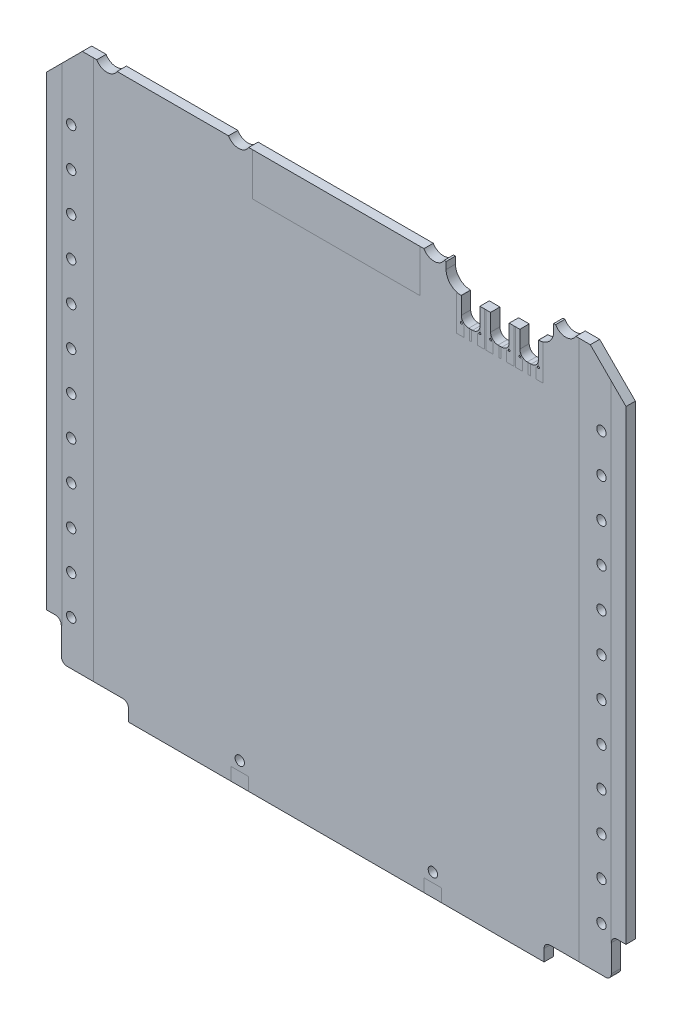
SolidWorks part; units mm, degrees
material "FR4_stuffedProtoboard"
ref_plane "Front Plane" through (0, 0, 0) normal (0, 0, 1) x (1, 0, 0)
ref_plane "Top Plane" through (0, 0, 0) normal (0, 1, 0) x (1, 0, 0)
ref_plane "Right Plane" through (0, 0, 0) normal (1, 0, 0) x (0, 0, -1)
ref_plane "Plane4" through (0, 0, -0.0125) normal (0, 0, -1) x (-1, 0, 0)
sketch "Sketch1" plane through (0, 0, -0.0125) normal (0, 0, -1) x (-1, 0, 0)
  line L4 (49.5, -50) -> (49.5, 45.3)
  line L6 (49.5, 45.3) -> (-49.5, 45.3)
  line L12 (-49.5, 45.3) -> (-49.5, -50)
  line L17 (-49.5, -50) -> (49.5, -50)
  line L18 (0, -50) -> (0, 45.3) construction
  dimension "D7" = 95.3
  dimension "D1" = 99
  dimension "D34" = 50
extrude "basicSize" add sketch "Sketch1" against normal blind 1.6
chamfer "Chamfer1" distance 6.1 angle 45 2 edges at (49.5, 45.3, 0.7875) (-49.5, 45.3, 0.7875)
sketch "Sketch4" plane through (0, 0, 1.5875) normal (0, 0, 1) x (1, 0, 0)
  line L1 (37.4679, 45.3) -> (40.9321, 45.3)
  line L7 (-43.4, 45.3) -> (43.4, 45.3) construction
  line L8 (49.5, 39.2) -> (49.5, -50) construction
  arc A0 (40.9321, 45.3) -> (37.4679, 45.3) centre (39.2, 46.3) cw
  point P5 (39.2, 44.3)
  dimension "D1" = 2
  dimension "D3" = 10.3
  dimension "D2" = 1
extrude "backplaneSideScrewCutout" cut sketch "Sketch4" against normal through all both and the other way through all
pattern_linear "LPattern3" count 2 spacing 22.5 along (-1, 0, 0) of "backplaneSideScrewCutout"
mirror "Mirror3" about plane through (0, 0, 0) normal (1, 0, 0) of "LPattern3"
sketch "Sketch6" plane through (0, 0, 1.5875) normal (0, 0, 1) x (1, 0, 0)
  line L0 (-49.5, -50) -> (-49.5, 39.2) construction
  line L1 (-49.5, -40.4) -> (-47, -40.4)
  line L2 (-49.5, -40.4) -> (-49.5, -50)
  line L4 (-47, -40.4) -> (-47, -47)
  line L5 (49.5, -50) -> (-49.5, -50) construction
  line L6 (-35.5, -50) -> (-49.5, -50)
  line L7 (-35.5, -50) -> (-35.5, -47)
  line L8 (-35.5, -47) -> (-47, -47)
  dimension "D1" = 2.5
  dimension "D2" = 3
  dimension "D3" = 9.6
  dimension "D4" = 14
extrude "Cut-Extrude4" cut sketch "Sketch6" against normal through all
fillet "Fillet1" radius 1 3 edges at (-35.5, -47, 0.7875) (-47, -47, 0.7875) (-47, -40.4, 0.7875)
mirror "Mirror1" about plane through (0, 0, 0) normal (1, 0, 0) of "Cut-Extrude4", "Fillet1"
sketch "Sketch7" plane through (0, 0, 1.5875) normal (0, 0, 1) x (1, 0, 0)
  line L0 (-14.2875, 45.5) -> (-14.2875, 39.912) construction
  line L1 (-14.2875, 45.3) -> (-14.2875, 38.007)
  line L2 (-12.2428, 38.007) -> (-11.8872, 38.007) construction
  line L3 (-14.2875, 38.007) -> (14.2875, 38.007)
  line L4 (14.2875, 45.5) -> (14.2875, 39.912) construction
  line L5 (14.2875, 45.3) -> (14.2875, 38.007)
  line L7 (-14.9679, 45.3) -> (14.9679, 45.3) construction
  line L8 (-14.2875, 45.3) -> (14.2875, 45.3)
extrude "TigerEyeFootprint" cut sketch "Sketch7" against normal blind 0.0001
sketch "thermalContacts_upper" plane through (0, 0, 1.5875) normal (0, 0, 1) x (1, 0, 0)
  line L0 (-49.5, -40.4) -> (-49.5, 39.2) construction
  line L1 (35.5, -50) -> (-35.5, -50) construction
  line L3 (-46.9, 45.3) -> (-46.9, -41.5)
  line L4 (-37.4679, 45.3) -> (-18.4321, 45.3) construction
  line L23 (-46.9, 45.3) -> (-56.3922, 45.3)
  line L24 (-56.3922, 45.3) -> (-56.3922, -41.5)
  line L25 (-56.3922, -41.5) -> (-46.9, -41.5)
  dimension "D1" = 2.6
  dimension "D2" = 8.5
extrude "keepOut_bottom" cut sketch "thermalContacts_upper" against normal blind 0.0001
sketch "Sketch3" plane through (0, 0, 1.5875) normal (0, 0, 1) x (1, 0, 0)
  line L1 (-47, -46) -> (-47, -41.5) construction
  line L2 (-36.5, -47) -> (-46, -47) construction
  line L3 (-14.9679, 45.3) -> (14.9679, 45.3) construction
  line L5 (-49.5, -40.4) -> (-49.5, 39.2) construction
  line L6 (-46.9, -41.5) -> (-46.9, 41.8) construction
  line L7 (-46.9, -41.5) -> (-47, -41.5)
  line L8 (-47, -46) -> (-47, -41.5) construction
  line L9 (-47, -41.5) -> (-46.9, -41.5) construction
  line L10 (0, -50) -> (0, 45.3) construction
  line L11 (35.5, -50) -> (-35.5, -50) construction
  line L12 (-43.4, 45.3) -> (-40.9321, 45.3) construction
  line L13 (-41.5, 45.3) -> (-46.9, 45.3)
  line L14 (-46, -47) -> (-41.5, -47)
  line L15 (-47, -41.5) -> (-47, -46)
  line L16 (-46.9, 45.3) -> (-46.9, -41.5)
  line L17 (-41.5, -47) -> (-41.5, 45.3)
  arc A3 (-47, -46) -> (-46, -47) centre (-46, -46) ccw construction
  arc A4 (-46, -47) -> (-47, -46) centre (-46, -46) cw
  dimension "D1" = 8
extrude "caution_top" cut sketch "Sketch3" against normal blind 0.0001
sketch "hold-downLocations" plane through (0, 0, 1.5875) normal (0, 0, 1) x (1, 0, 0)
  line L1 (-18, -47.8) -> (-15, -47.8) construction
  line L3 (15, -47.8) -> (18, -47.8)
  line L4 (18, -47.8) -> (18, -50)
  line L5 (35.5, -50) -> (-35.5, -50) construction
  line L6 (18, -50) -> (15, -50)
  line L7 (15, -50) -> (15, -47.8)
  line L8 (-15, -47.8) -> (-15, -50) construction
  line L9 (-15, -50) -> (-18, -50) construction
  line L10 (-18, -50) -> (-18, -47.8) construction
  line L11 (0, -50) -> (0, -47.8) construction
  line L12 (-15, -47.8) -> (15, -47.8) construction
  dimension "D1" = 3
  dimension "D2" = 2.2
  dimension "D3" = 3
  dimension "D5" = 30
extrude "hold-downFootprints" cut sketch "hold-downLocations" against normal blind 0.0001
ref_plane "midplane_Z" through (0, 0, 0.7875) normal (0, 0, 1) x (1, 0, 0)
mirror "clearances_top-bottom" about plane through (0, 0, 0.7875) normal (0, 0, 1) of "hold-downFootprints", "caution_top", "keepOut_bottom"
mirror "clearances_side-side" about plane through (0, 0, 0) normal (1, 0, 0) of "clearances_top-bottom"
sketch "Sketch10" plane through (0, 0, -0.0125) normal (0, 0, -1) x (-1, 0, 0)
  line L0 (-15, -47.8) -> (-15, -50) construction
  line L1 (-18, -47.8) -> (-15, -47.8)
  line L2 (-18, -47.8) -> (-18, -44.5)
  line L3 (-18, -44.5) -> (-15, -44.5)
  line L4 (-15, -47.8) -> (-15, -44.5)
  line L5 (-15, -50) -> (15, -50) construction
  line L6 (0, -50) -> (0, -41.5199) construction
  line L7 (15, -47.8) -> (15, -44.5)
  line L8 (18, -44.5) -> (15, -44.5)
  line L9 (18, -47.8) -> (18, -44.5)
  line L10 (18, -47.8) -> (15, -47.8)
  dimension "D1" = 5.5
extrude "bottomsideShelfKeepouts" cut sketch "Sketch10" against normal up to surface (0.0001 mm away) up to face at (16.5, -48.9, -0.0124)
sketch "recommendedBuildArea" [suppressed] plane through (0, 0, 1.5875) normal (0, 0, 1) x (1, 0, 0)
  line L0 (51.1146, 38.007) -> (51.1146, 56.8216) construction
  line L1 (-35.5, -45.5) -> (-46.8, -45.5) construction
  line L2 (-35.5, -47) -> (-35.5, -45.5) construction
  line L3 (35.5, -47) -> (35.5, -45.5) construction
  line L4 (14.2875, 45.3) -> (-14.2875, 45.3)
  line L5 (-14.2875, 45.3) -> (-14.2875, 38.007)
  line L6 (-14.2875, 38.007) -> (14.2875, 38.007)
  line L7 (-46.8, 41.9) -> (-49.5, 39.2)
  line L8 (-49.5, 39.2) -> (-49.5, -40.4)
  line L9 (-49.5, -40.4) -> (-48, -40.4)
  line L10 (-46.8, -41.5) -> (-46.8, 41.9)
  line L11 (-47, -41.4) -> (-47, -41.5)
  line L12 (-47, -41.4) -> (-47, -41.5)
  line L13 (-47, -41.5) -> (-46.8, -41.5)
  line L14 (35.5, -45.5) -> (46.8, -45.5) construction
  line L15 (54.1146, 35.007) -> (54.1146, 77.997)
  line L16 (54.1146, 77.997) -> (43.8, 42.325)
  line L17 (-46.8, -45.5) -> (-46.8, 41.9) construction
  line L20 (43.8, 42.325) -> (43.8, -42.5)
  line L21 (14.2875, 38.007) -> (14.2875, 45.3)
  line L22 (32.5, -42.5) -> (43.8, -42.5)
  line L23 (-14.2875, 45.3) -> (-14.2875, 38.007)
  line L24 (-14.2875, 38.007) -> (51.1146, 38.007)
  line L25 (32.5, -47) -> (32.5, -42.5)
  line L26 (32.5, -47) -> (32.5, -47)
  line L27 (21, -47) -> (32.5, -47)
  line L28 (21, -45) -> (21, -47)
  line L29 (46.8, -41.5) -> (47, -41.5)
  line L30 (46.8, -41.5) -> (47, -41.5)
  line L31 (46.8, 41.9) -> (46.8, -41.5)
  line L32 (48, -40.4) -> (49.5, -40.4)
  line L33 (49.5, -40.4) -> (49.5, 39.2)
  line L34 (49.5, 39.2) -> (46.8, 41.9)
  line L35 (47, -41.5) -> (47, -41.4)
  line L36 (12, -45) -> (21, -45)
  line L37 (47, -41.5) -> (47, -41.4)
  line L38 (46.8, 41.9) -> (46.8, -45.5) construction
  line L39 (12, -47) -> (12, -45)
  line L40 (-12, -47) -> (12, -47)
  line L41 (-12, -45) -> (-12, -47)
  line L42 (-21, -45) -> (-12, -45)
  line L43 (-21, -47) -> (-21, -45)
  line L44 (-32.5, -47) -> (-21, -47)
  line L45 (-32.5, -47) -> (-32.5, -47)
  line L46 (-32.5, -47) -> (-32.5, -42.5)
  line L47 (-32.5, -42.5) -> (-43.8, -42.5)
  line L48 (-43.8, -42.5) -> (-43.8, 34.7661)
  line L49 (-43.8, 34.7661) -> (-43.8, 34.7661)
  line L50 (-43.8, 34.7661) -> (-39.8793, 42.3)
  line L51 (-17.2875, 42.3) -> (-39.8793, 42.3)
  line L52 (-17.2875, 42.3) -> (-17.2875, 35.007)
  line L53 (-17.2875, 35.007) -> (54.1146, 35.007)
  line L59 (-47, -41.5) -> (-46.8, -41.5)
  line L72 (-15, -48) -> (-15, -50)
  line L73 (-15, -50) -> (15, -50)
  line L74 (15, -50) -> (15, -48)
  line L75 (15, -48) -> (18, -48)
  line L76 (18, -48) -> (18, -50)
  line L77 (18, -50) -> (35.5, -50)
  line L78 (35.5, -50) -> (35.5, -48)
  line L79 (36.5, -47) -> (41.5, -47)
  line L80 (41.5, -47) -> (41.5, 45.3)
  line L81 (41.5, 45.3) -> (40.9321, 45.3)
  line L82 (37.4679, 45.3) -> (34.25, 45.3)
  line L83 (34.25, 45.3) -> (34.25, 38.35)
  line L84 (34.25, 38.35) -> (30.75, 38.35)
  line L85 (30.75, 38.35) -> (30.75, 45.3)
  line L86 (30.75, 45.3) -> (29.25, 45.3)
  line L87 (29.25, 45.3) -> (29.25, 38.35)
  line L88 (29.25, 38.35) -> (25.75, 38.35)
  line L89 (25.75, 38.35) -> (25.75, 45.3)
  line L90 (25.75, 45.3) -> (24.25, 45.3)
  line L91 (24.25, 45.3) -> (24.25, 38.35)
  line L92 (24.25, 38.35) -> (20.75, 38.35)
  line L93 (20.75, 38.35) -> (20.75, 45.3)
  line L94 (20.75, 45.3) -> (18.4321, 45.3)
  line L95 (14.9679, 45.3) -> (14.2875, 45.3)
  line L96 (14.2875, 45.3) -> (14.2875, 38.007)
  line L97 (14.2875, 38.007) -> (-14.2875, 38.007)
  line L98 (-14.2875, 38.007) -> (-14.2875, 45.3)
  line L99 (-14.2875, 45.3) -> (-14.9679, 45.3)
  line L100 (-18.4321, 45.3) -> (-37.4679, 45.3)
  line L101 (-40.9321, 45.3) -> (-41.5, 45.3)
  line L102 (41.5, -47) -> (41.5, 45.3)
  line L103 (-41.5, -47) -> (-36.5, -47)
  line L104 (-35.5, -48) -> (-35.5, -50)
  line L105 (-35.5, -50) -> (-18, -50)
  line L106 (-18, -50) -> (-18, -48)
  line L107 (-18, -48) -> (-15, -48)
  line L108 (-15, -48) -> (-15, -50) construction
  line L109 (-15, -50) -> (15, -50) construction
  line L110 (15, -50) -> (15, -48) construction
  line L111 (15, -48) -> (18, -48) construction
  line L112 (18, -48) -> (18, -50) construction
  line L113 (18, -50) -> (35.5, -50) construction
  line L114 (35.5, -50) -> (35.5, -47) construction
  line L115 (35.5, -47) -> (41.5, -47) construction
  line L133 (51.1146, 38.007) -> (-14.2875, 38.007)
  line L134 (-14.2875, 38.007) -> (-14.2875, 45.3)
  line L136 (-14.2875, 45.3) -> (-41.7, 45.3) construction
  line L139 (-41.5, -47) -> (-35.5, -47) construction
  line L140 (-35.5, -47) -> (-35.5, -50) construction
  line L141 (-35.5, -50) -> (-18, -50) construction
  line L142 (-18, -50) -> (-18, -48) construction
  line L143 (-18, -48) -> (-15, -48) construction
  line L144 (-46.8, 35.5) -> (-41.7, 45.3) construction
  line L160 (-41.5, 45.3) -> (-41.5, -47)
  line L161 (-41.5, 45.3) -> (-41.5, -47)
  line L162 (-46.8, 41.9) -> (-46.8, 35.5) construction
  line L163 (51.1146, 56.8216) -> (46.8, 41.9) construction
  arc A1 (-47, -41.4) -> (-48, -40.4) centre (-48, -41.4) ccw
  arc A3 (48, -40.4) -> (47, -41.4) centre (48, -41.4) ccw
  arc A10 (36.5, -47) -> (35.5, -48) centre (36.5, -48) ccw
  arc A11 (37.4679, 45.3) -> (40.9321, 45.3) centre (39.2, 46.3) ccw
  arc A12 (14.9679, 45.3) -> (18.4321, 45.3) centre (16.7, 46.3) ccw
  arc A13 (-18.4321, 45.3) -> (-14.9679, 45.3) centre (-16.7, 46.3) ccw
  arc A14 (-40.9321, 45.3) -> (-37.4679, 45.3) centre (-39.2, 46.3) ccw
  arc A15 (-35.5, -48) -> (-36.5, -47) centre (-36.5, -48) ccw
  dimension "D5" = 1.5
  dimension "D1" = 0
  dimension "D2" = 0
  dimension "D3" = 0
  dimension "D4" = 0
  dimension "D6" = 3
ref_point "rail midpoint"
sketch "locatorSketch" plane through (0, 0, 1.5875) normal (0, 0, 1) x (1, 0, 0)
  line L0 (-12.2428, 39.531) -> (12.2428, 38.007) construction
  line L1 (12.2428, 39.531) -> (-12.2428, 38.007) construction
  line L2 (-21.9628, 39.277) -> (-33.0372, 38.261) construction
  line L3 (-33.0372, 39.277) -> (-21.9628, 38.261) construction
  line L4 (-12.2428, 38.261) -> (-12.2428, 38.007)
  line L5 (-11.8872, 38.261) -> (-12.2428, 38.261)
  line L6 (-11.8872, 38.007) -> (-11.8872, 38.261)
  line L7 (-12.2428, 38.007) -> (-11.8872, 38.007)
  line L8 (-12.2428, 38.261) -> (-12.2428, 38.007)
  line L9 (-11.8872, 38.261) -> (-12.2428, 38.261)
  line L10 (-11.8872, 38.007) -> (-11.8872, 38.261)
  line L11 (-12.2428, 38.007) -> (-11.8872, 38.007)
  line L12 (-12.2428, 39.531) -> (-12.2428, 39.277)
  line L13 (-11.8872, 39.531) -> (-12.2428, 39.531)
  line L14 (-11.8872, 39.277) -> (-11.8872, 39.531)
  line L15 (-12.2428, 39.277) -> (-11.8872, 39.277)
  line L16 (-12.2428, 39.531) -> (-12.2428, 39.277)
  line L17 (-11.8872, 39.531) -> (-12.2428, 39.531)
  line L18 (-11.8872, 39.277) -> (-11.8872, 39.531)
  line L19 (-12.2428, 39.277) -> (-11.8872, 39.277)
  line L20 (11.8872, 39.531) -> (11.8872, 39.277)
  line L21 (12.2428, 39.531) -> (11.8872, 39.531)
  line L22 (12.2428, 39.277) -> (12.2428, 39.531)
  line L23 (11.8872, 39.277) -> (12.2428, 39.277)
  line L24 (11.8872, 39.531) -> (11.8872, 39.277)
  line L25 (12.2428, 39.531) -> (11.8872, 39.531)
  line L26 (12.2428, 39.277) -> (12.2428, 39.531)
  line L27 (11.8872, 39.277) -> (12.2428, 39.277)
  line L28 (11.8872, 38.261) -> (11.8872, 38.007)
  line L29 (12.2428, 38.261) -> (11.8872, 38.261)
  line L30 (12.2428, 38.007) -> (12.2428, 38.261)
  line L31 (11.8872, 38.007) -> (12.2428, 38.007)
  line L32 (11.8872, 38.261) -> (11.8872, 38.007)
  line L33 (12.2428, 38.261) -> (11.8872, 38.261)
  line L34 (12.2428, 38.007) -> (12.2428, 38.261)
  line L35 (11.8872, 38.007) -> (12.2428, 38.007)
  line L38 (-21.9628, 39.531) -> (-21.9628, 39.277)
  line L39 (-21.6072, 39.531) -> (-21.9628, 39.531)
  line L40 (-21.6072, 39.277) -> (-21.6072, 39.531)
  line L41 (-21.9628, 39.277) -> (-21.6072, 39.277)
  line L42 (-21.9628, 39.531) -> (-21.9628, 39.277)
  line L43 (-21.6072, 39.531) -> (-21.9628, 39.531)
  line L44 (-21.6072, 39.277) -> (-21.6072, 39.531)
  line L45 (-21.9628, 39.277) -> (-21.6072, 39.277)
  line L46 (-33.3928, 38.261) -> (-33.3928, 38.007)
  line L47 (-33.0372, 38.261) -> (-33.3928, 38.261)
  line L48 (-33.0372, 38.007) -> (-33.0372, 38.261)
  line L49 (-33.3928, 38.007) -> (-33.0372, 38.007)
  line L50 (-33.3928, 38.261) -> (-33.3928, 38.007)
  line L51 (-33.0372, 38.261) -> (-33.3928, 38.261)
  line L52 (-33.0372, 38.007) -> (-33.0372, 38.261)
  line L53 (-33.3928, 38.007) -> (-33.0372, 38.007)
  line L55 (-21.9628, 38.261) -> (-21.9628, 38.007)
  line L56 (-21.6072, 38.261) -> (-21.9628, 38.261)
  line L57 (-21.6072, 38.007) -> (-21.6072, 38.261)
  line L58 (-21.9628, 38.007) -> (-21.6072, 38.007)
  line L59 (-21.9628, 38.261) -> (-21.9628, 38.007)
  line L60 (-21.6072, 38.261) -> (-21.9628, 38.261)
  line L61 (-21.6072, 38.007) -> (-21.6072, 38.261)
  line L62 (-21.9628, 38.007) -> (-21.6072, 38.007)
  line L63 (-33.3928, 39.531) -> (-33.3928, 39.277)
  line L64 (-33.0372, 39.531) -> (-33.3928, 39.531)
  line L65 (-33.0372, 39.277) -> (-33.0372, 39.531)
  line L66 (-33.3928, 39.277) -> (-33.0372, 39.277)
  line L67 (-33.3928, 39.531) -> (-33.3928, 39.277)
  line L68 (-33.0372, 39.531) -> (-33.3928, 39.531)
  line L69 (-33.0372, 39.277) -> (-33.0372, 39.531)
  line L70 (-33.3928, 39.277) -> (-33.0372, 39.277)
  dimension "D1" = 0
  dimension "D2" = 0
  dimension "D3" = 0
  dimension "D4" = 0
  dimension "D5" = 0
  dimension "D6" = 0
  dimension "D7" = 0
  dimension "D8" = 0
sketch "Sketch8" plane through (0, 0, 1.5875) normal (0, 0, 1) x (1, 0, 0)
  line L0 (-49.5, -40.4) -> (-48, -40.4) construction
  line L2 (-49.5, -40.4) -> (-49.5, 39.2) construction
  line L3 (-41.5, 45.3) -> (-43.4, 45.3) construction
  line L4 (-18, -47.8) -> (-15, -47.8) construction
  line L5 (-45.3, 33.5) -> (-46.9, 33.5) construction
  line L6 (-46.9, 41.8) -> (-46.9, -41.5) construction
  line L7 (-16.5, -46.2) -> (-16.5, -47.8) construction
  line L8 (-18, -47.8) -> (-15, -47.8) construction
  circle A0 centre (-45.3, 33.5) radius 0.8
  circle A1 centre (-45.3, 26.8727) radius 0.8
  circle A2 centre (-45.3, 20.2455) radius 0.8
  circle A3 centre (-45.3, 13.6182) radius 0.8
  circle A4 centre (-45.3, 6.9909) radius 0.8
  circle A5 centre (-45.3, 0.3636) radius 0.8
  circle A6 centre (-45.3, -6.2636) radius 0.8
  circle A7 centre (-45.3, -12.8909) radius 0.8
  circle A8 centre (-45.3, -19.5182) radius 0.8
  circle A9 centre (-45.3, -26.1455) radius 0.8
  circle A10 centre (-45.3, -32.7727) radius 0.8
  circle A11 centre (-45.3, -39.4) radius 0.8
  circle A12 centre (-16.5, -46.2) radius 0.8
  point P35 (-16.5, -47.8)
  dimension "D1" = 1.6
  dimension "D3" = 1
  dimension "D5" = 4.2
  dimension "D6" = 11.8
  dimension "D2" = 12
extrude "springPinHoleSeed" cut sketch "Sketch8" against normal blind 10
mirror "Mirror4" about plane through (0, 0, 0) normal (1, 0, 0) of "springPinHoleSeed"
sketch "Sketch9" plane through (0, 0, 1.5875) normal (0, 0, 1) x (1, 0, 0)
  circle A0 centre (-45.3, 33.5) radius 1.35
  dimension "D1" = 2.7
sketch "bottomsideKeepout_trace" plane through (0, 0, -0.0125) normal (0, 0, -1) x (-1, 0, 0)
  line L0 (18, -50) -> (18, -44.5) construction
  line L1 (18, -44.5) -> (15, -44.5) construction
  line L2 (15, -44.5) -> (15, -50) construction
  line L3 (-15, -44.5) -> (-15, -50) construction
  line L4 (-15, -44.5) -> (-18, -44.5) construction
  line L5 (-18, -50) -> (-18, -44.5) construction
  line L6 (18, -50) -> (18, -44.5)
  line L7 (18, -44.5) -> (15, -44.5)
  line L8 (15, -44.5) -> (15, -50)
  line L9 (-15, -44.5) -> (-15, -50)
  line L10 (-15, -44.5) -> (-18, -44.5)
  line L11 (-18, -50) -> (-18, -44.5)
  line L12 (15, -50) -> (18, -50) construction
  line L13 (-15, -50) -> (-18, -50) construction
  line L14 (15, -50) -> (18, -50)
  line L15 (-15, -50) -> (-18, -50)
sketch "Sketch11" plane through (0, 0, 1.5875) normal (0, 0, 1) x (1, 0, 0)
  line L6 (34.54, 41.56) -> (31.36, 41.56)
  line L8 (34.54, 41.56) -> (34.54, 37.36)
  line L11 (34.54, 37.36) -> (31.36, 37.36)
  line L12 (31.36, 41.56) -> (31.36, 37.36)
  line L13 (34.54, 41.56) -> (31.36, 37.36) construction
  line L14 (34.54, 37.36) -> (31.36, 41.56) construction
  line L18 (29.54, 41.56) -> (26.36, 41.56)
  line L19 (29.54, 41.56) -> (29.54, 37.36)
  line L20 (29.54, 37.36) -> (26.36, 37.36)
  line L21 (26.36, 41.56) -> (26.36, 37.36)
  line L22 (29.54, 41.56) -> (26.36, 37.36) construction
  line L23 (29.54, 37.36) -> (26.36, 41.56) construction
  line L24 (24.54, 41.56) -> (21.36, 41.56)
  line L25 (24.54, 41.56) -> (24.54, 37.36)
  line L26 (24.54, 37.36) -> (21.36, 37.36)
  line L27 (21.36, 41.56) -> (21.36, 37.36)
  line L28 (24.54, 41.56) -> (21.36, 37.36) construction
  line L29 (24.54, 37.36) -> (21.36, 41.56) construction
  line L30 (18.4321, 45.3) -> (37.4679, 45.3) construction
  line L31 (16.7, 46.3) -> (39.2, 46.3) construction
  point P4 (32.95, 39.46)
  point P10 (27.95, 46.3)
  point P11 (0, 0)
  point P15 (27.95, 39.46)
  point P20 (22.95, 39.46)
  dimension "D5" = 5
  dimension "D1" = 3.18
  dimension "D2" = 4.2
  dimension "D4" = 3
  dimension "D6" = 3.74
extrude "Cut-Extrude5" cut sketch "Sketch11" against normal blind 10
fillet "Fillet2" radius 1.27 6 edges at (24.54, 37.36, 0.7875) (29.54, 37.36, 0.7875) (34.54, 37.36, 0.7875) (31.36, 37.36, 0.7875) (26.36, 37.36, 0.7875) (21.36, 37.36, 0.7875)
hole_wizard "Ø0.32 (0.32) Diameter Hole1" positions "Sketch12" profile "Sketch13" hole size "Ø0.32" standard "ANSI Metric"
sketch "Sketch12" plane through (0, 0, 1.5875) normal (0, 0, 1) x (1, 0, 0)
  line L1 (34.54, 38.63) -> (34.54, 41.56) construction
  line L2 (31.36, 41.56) -> (31.36, 38.63) construction
  line L3 (32.95, 37.36) -> (34.7997, 37.36) construction
  line L4 (32.63, 37.36) -> (33.27, 37.36) construction
  point P0 (34.54, 37.52)
  point P2 (31.36, 37.52)
  point P16 (29.54, 37.52)
  point P17 (26.36, 37.52)
  point P18 (24.54, 37.52)
  point P19 (21.36, 37.52)
  dimension "D2" = 5
  dimension "D3" = 0.16
  dimension "D1" = 3
sketch "Sketch13" plane through (34.54, 37.52, 1.5875) normal (1, 0, 0) x (0, -1, 0)
  line L0 (0, 0) -> (0, 9.6211)
  line L1 (0, 9.6211) -> (0.16, 9.525)
  line L2 (0.16, 9.525) -> (0.16, 0)
  line L5 (0.16, 0) -> (0, 0)
  line L10 (0, 9.6211) -> (-0.16, 9.525) construction
  line L11 (0, -6.35) -> (0, 107.95) construction
  dimension "Hole Dia." = 0.32
  dimension "Hole Depth" = 9.525
  dimension "Drill Angle" = 118
sketch "Sketch14" plane through (0, 0, 1.5875) normal (0, 0, 1) x (1, 0, 0)
  line L1 (35.325, 41.56) -> (34.54, 41.56)
  line L2 (35.325, 41.56) -> (35.325, 35.57)
  line L3 (35.325, 35.57) -> (34.095, 35.57)
  line L4 (30.575, 41.56) -> (30.575, 35.57)
  line L5 (35.325, 41.56) -> (30.575, 35.57) construction
  line L6 (35.325, 35.57) -> (30.575, 41.56) construction
  line L7 (32.95, 37.36) -> (32.95, 35.57) construction
  line L8 (32.63, 37.36) -> (33.27, 37.36) construction
  line L9 (31.805, 35.57) -> (31.805, 37.36)
  line L10 (32.76, 37.36) -> (33.14, 37.36)
  line L11 (32.76, 37.36) -> (32.76, 35.57)
  line L12 (32.76, 35.57) -> (33.14, 35.57)
  line L13 (33.14, 37.36) -> (33.14, 35.57)
  line L14 (32.76, 37.36) -> (33.14, 35.57) construction
  line L15 (32.76, 35.57) -> (33.14, 37.36) construction
  line L16 (34.095, 35.57) -> (34.095, 37.36)
  line L17 (33.14, 35.57) -> (32.76, 35.57)
  line L18 (31.36, 41.56) -> (31.36, 38.63) construction
  line L19 (34.54, 38.63) -> (34.54, 41.56) construction
  line L20 (31.36, 41.56) -> (31.36, 38.63)
  line L21 (34.54, 38.63) -> (34.54, 41.56)
  line L22 (32.76, 37.36) -> (33.14, 37.36)
  line L23 (31.36, 41.56) -> (30.575, 41.56)
  line L24 (31.805, 37.36) -> (31.36, 37.36)
  line L25 (34.095, 37.36) -> (34.54, 37.36)
  line L26 (31.36, 37.68) -> (31.36, 38.63)
  line L27 (34.54, 37.68) -> (34.54, 38.63)
  line L28 (31.805, 35.57) -> (30.575, 35.57)
  circle A2 centre (31.36, 37.52) radius 0.16 construction
  circle A3 centre (34.54, 37.52) radius 0.16 construction
  arc A6 (31.36, 37.68) -> (31.36, 37.36) centre (31.36, 37.52) ccw
  arc A7 (34.54, 37.36) -> (34.54, 37.68) centre (34.54, 37.52) ccw
  point P4 (32.95, 38.565)
  point P10 (31.9131, 39.0621)
  point P15 (32.95, 36.465)
  point P26 (0, 0)
  dimension "D1" = 5.99
  dimension "D2" = 4.75
  dimension "D3" = 2.29
  dimension "D4" = 0.38
extrude "Boss-Extrude1" add sketch "Sketch14" along normal blind 0.0001 contours A6 L26 L20 L23 L4 L28 L9 L24 | L13 L10 L11 L12 | A7 L25 L16 L3 L2 L1 L21 L27 region at (34.8451, 38.2662, 1.5875) region at (31.0549, 38.2662, 1.5875) region at (32.95, 36.465, 1.5875)
pattern_linear "LPattern4" count 3 spacing 5 along (-1, 0, 0) of "Boss-Extrude1"
sketch "Sketch15" plane through (0, 0, 1.5875) normal (0, 0, 1) x (1, 0, 0)
  line L0 (18.4321, 45.3) -> (37.4679, 45.3) construction
  line L1 (18.76, 45.3) -> (37.14, 45.3)
  line L2 (18.76, 45.3) -> (18.76, 44.1)
  line L3 (21.3, 41.56) -> (34.6, 41.56)
  line L4 (37.14, 45.3) -> (37.14, 44.1)
  line L5 (18.76, 45.3) -> (37.14, 41.56) construction
  line L6 (18.76, 41.56) -> (37.14, 45.3) construction
  line L7 (34.54, 41.56) -> (31.36, 41.56) construction
  line L9 (21.36, 37.68) -> (21.36, 41.56) construction
  line L11 (34.54, 37.68) -> (34.54, 41.56) construction
  arc A0 (34.6, 41.56) -> (37.14, 44.1) centre (34.6, 44.1) ccw
  arc A1 (18.76, 44.1) -> (21.3, 41.56) centre (21.3, 44.1) ccw
  point P4 (27.95, 43.43)
  dimension "D3" = 2.54
  dimension "D1" = 2.6
  dimension "D2" = 2.6
extrude "Cut-Extrude6" cut sketch "Sketch15" against normal through all and the other way through all
